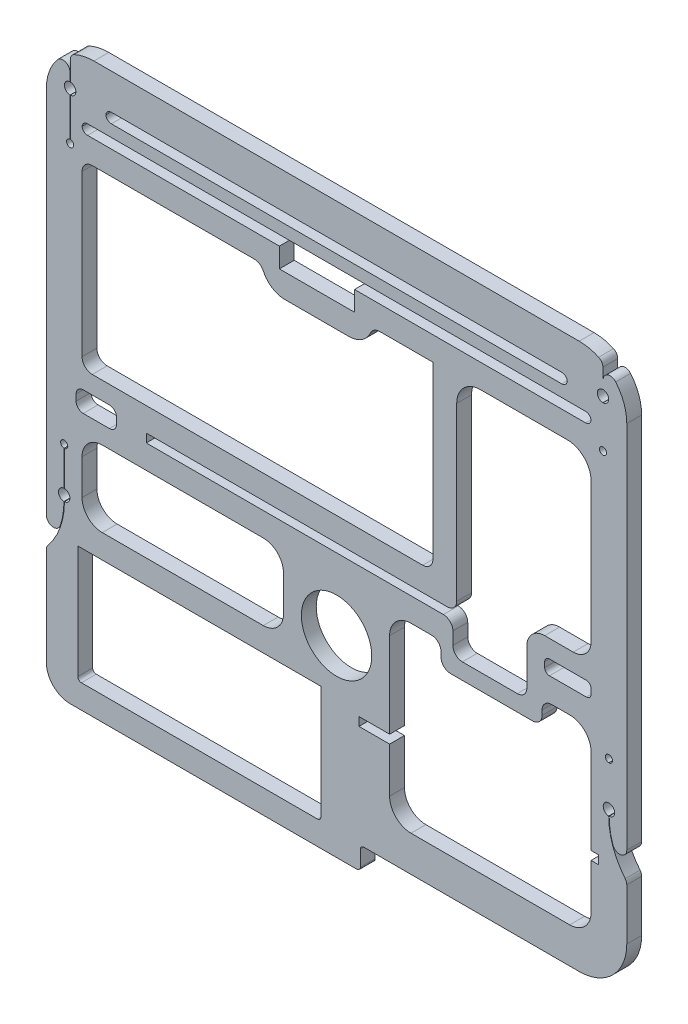
SolidWorks part; units mm, degrees
ref_plane "Front Plane" through (0, 0, 0) normal (0, 0, 1) x (1, 0, 0)
ref_plane "Top Plane" through (0, 0, 0) normal (0, 1, 0) x (1, 0, 0)
ref_plane "Right Plane" through (0, 0, 0) normal (1, 0, 0) x (0, 0, -1)
sketch "Sketch1" plane through (0, 0, 0) normal (0, 0, 1) x (1, 0, 0)
  line L0 (63.9883, 88.3985) -> (63.9883, 84.5885) construction
  line L1 (48.2422, 30.1083) -> (110.2188, 30.1083)
  line L2 (48.2422, 30.1083) -> (48.2422, 88.3985)
  line L3 (48.2422, 88.3985) -> (110.2188, 88.3985)
  line L4 (110.2188, 30.1083) -> (110.2188, 88.3985)
  line L5 (106.4088, 84.5885) -> (52.0522, 84.5885)
  line L6 (106.4088, 84.5885) -> (106.4088, 33.9183)
  line L7 (106.4088, 33.9183) -> (52.0522, 33.9183)
  line L8 (52.0522, 84.5885) -> (52.0522, 33.9183)
  line L9 (63.9883, 86.4935) -> (18.0707, 86.4935) construction
  line L10 (52.0522, 41.2855) -> (48.2422, 41.2855) construction
  line L11 (50.1472, 41.2855) -> (50.1472, 25.8577) construction
  line L12 (13.5248, 33.9183) -> (13.5248, 30.1083) construction
  line L13 (13.5248, 32.0133) -> (21.1598, 32.0133) construction
  line L14 (110.2188, 38.1916) -> (106.4088, 38.1916) construction
  line L15 (108.3138, 38.1916) -> (108.3138, 22.3321) construction
  line L16 (106.4088, 54.6152) -> (106.4088, 79.5085) construction
  line L17 (52.0522, 74.5555) -> (52.0522, 54.6152) construction
  line L22 (79.0876, 86.4935) -> (79.6338, 86.4935) construction
  line L23 (96.5564, 32.0133) -> (96.0102, 32.0133) construction
  dimension "D1" = 3.81
  dimension "D2" = 3.81
extrude "Boss-Extrude1" add sketch "Sketch1" along normal blind 1.5875
sketch "Sketch2" plane through (0, 0, 0) normal (0, 0, -1) x (-1, 0, 0)
  line L0 (-106.4088, 33.9183) -> (-106.4088, 84.5885) construction
  line L1 (-106.4088, 55.8724) -> (-52.0522, 55.8724)
  line L2 (-106.4088, 55.8724) -> (-106.4088, 53.3324)
  line L3 (-106.4088, 53.3324) -> (-52.0522, 53.3324)
  line L4 (-52.0522, 55.8724) -> (-52.0522, 53.3324)
  line L5 (-52.0522, 84.5885) -> (-52.0522, 33.9183) construction
  line L7 (-99.5505, 55.8724) -> (-58.9105, 55.8724) construction
  line L8 (-99.4108, 81.1849) -> (-61.0568, 81.1849) construction
  line L9 (-80.5132, 79.0767) -> (-73.7568, 79.0767) construction
  line L10 (-80.5132, 81.1849) -> (-80.5132, 79.0767) construction
  line L11 (-106.4088, 81.1849) -> (-81.1482, 81.1849)
  line L12 (-106.4088, 81.1849) -> (-106.4088, 78.6449)
  line L13 (-106.4088, 78.6449) -> (-83.0532, 78.6449)
  line L14 (-52.0522, 81.1849) -> (-52.0522, 78.6449)
  line L15 (-106.4088, 83.5217) -> (-52.0522, 83.5217)
  line L16 (-106.4088, 83.5217) -> (-106.4088, 82.2517)
  line L17 (-106.4088, 82.2517) -> (-52.0522, 82.2517)
  line L18 (-52.0522, 83.5217) -> (-52.0522, 82.2517)
  line L19 (-73.7568, 79.0767) -> (-73.7568, 81.1849) construction
  line L20 (-80.5132, 81.1849) -> (-80.5132, 79.0767) construction
  line L21 (-73.7568, 79.0767) -> (-73.7568, 81.1849) construction
  line L22 (-81.1482, 79.0767) -> (-81.1482, 81.1849)
  line L23 (-73.1218, 79.0767) -> (-81.1482, 79.0767)
  line L24 (-73.1218, 79.0767) -> (-73.1218, 81.1849)
  line L25 (-83.0532, 78.6449) -> (-83.0532, 76.5367)
  line L26 (-83.0532, 76.5367) -> (-71.2168, 76.5367)
  line L27 (-71.2168, 76.5367) -> (-71.2168, 78.6449)
  line L28 (-71.2168, 78.6449) -> (-52.0522, 78.6449)
  line L29 (-73.1218, 81.1849) -> (-52.0522, 81.1849)
  line L30 (-81.1482, 71.7401) -> (-80.5132, 71.7401) construction
  line L31 (-57.9086, 84.5885) -> (-57.9086, 83.5217) construction
  line L32 (-73.7568, 71.6584) -> (-73.1218, 71.6584) construction
  line L33 (-106.4088, 84.5885) -> (-52.0522, 84.5885) construction
  line L35 (-57.9086, 82.2517) -> (-57.9086, 81.1849) construction
  dimension "D1" = 2.54
  dimension "D2" = 1.905
  dimension "D3" = 2.54
  dimension "D4" = 1.905
  dimension "D5" = 1.27
  dimension "D6" = 0.635
extrude "Boss-Extrude2" add sketch "Sketch2" against normal up to surface (1.5875 mm away) up to face at (79.2305, 59.2534, 1.5875)
sketch "Sketch3" plane through (0, 0, 0) normal (0, 0, -1) x (-1, 0, 0)
  line L0 (-92.0575, 59.3268) -> (-92.0575, 56.7868) construction
  line L3 (-58.9105, 56.7868) -> (-99.5505, 56.7868) construction
  line L12 (-92.0575, 56.7868) -> (-13.0532, 56.7868)
  line L13 (-13.0532, 56.7868) -> (-52.0522, 56.7868)
  line L14 (-52.0522, 78.6449) -> (-52.0522, 55.8724) construction
  line L15 (-52.0522, 56.7868) -> (-52.0522, 59.3268)
  line L16 (-52.0522, 59.3268) -> (-89.5175, 59.3268)
  line L17 (-89.5175, 59.3268) -> (-89.5175, 78.6449)
  line L18 (-71.2168, 78.6449) -> (-52.0522, 78.6449) construction
  line L19 (-89.5175, 78.6449) -> (-92.0575, 78.6449)
  line L20 (-92.0575, 78.6449) -> (-92.0575, 56.7868)
  line M27 (-71.2168, 78.6449) -> (-52.0522, 78.6449)
  line M28 (-52.0522, 78.6449) -> (-52.0522, 55.8724)
  dimension "D3" = 2.54
  dimension "D4" = 2.54
extrude "Boss-Extrude3" add sketch "Sketch3" against normal up to surface (1.5875 mm away) contours L20 L12 L13 L16 L17 M27 M28 region at (91.6016, 67.7159, 0) up to face at (79.2305, 84.0551, 1.5875)
sketch "Sketch14" plane through (0, 0, 1.5875) normal (0, 0, 1) x (1, 0, 0)
  line L0 (77.0492, 42.694) -> (51.5984, 42.694) construction
  line L1 (84.8947, 41.932) -> (84.8947, 50.7924) construction
  line L2 (84.8947, 33.9183) -> (84.8947, 53.3324)
  line L4 (77.0492, 42.694) -> (52.0522, 42.694)
  line L5 (52.0522, 53.3324) -> (52.0522, 33.9183) construction
  line L6 (52.0522, 53.3324) -> (106.4088, 53.3324) construction
  line L7 (52.0522, 33.9183) -> (106.4088, 33.9183) construction
  line L9 (77.0492, 42.694) -> (77.0492, 33.9183)
  line L10 (77.0492, 33.9183) -> (84.8947, 33.9183)
  line L11 (52.0522, 53.3324) -> (84.8947, 53.3324)
  line L12 (52.0522, 53.3324) -> (52.0522, 42.694)
extrude "Boss-Extrude9" add sketch "Sketch14" against normal up to surface (1.5875 mm away) up to face at (83.5062, 63.768, 0)
sketch "Sketch5" plane through (0, 0, 0) normal (0, 0, -1) x (-1, 0, 0)
  line L1 (-51.5984, 30.2353) -> (-77.5572, 30.2353) construction
  line L2 (-51.5984, 30.2353) -> (-51.5984, 42.694) construction
  line L6 (-51.5984, 42.694) -> (-77.5572, 42.694) construction
  line L7 (-77.5572, 30.2353) -> (-77.5572, 42.694) construction
  line L8 (-51.5984, 30.2353) -> (-77.5572, 30.2353)
  line L9 (-51.5984, 30.2353) -> (-51.5984, 42.694)
  line L10 (-51.5984, 42.694) -> (-77.5572, 42.694)
  line L11 (-77.5572, 30.2353) -> (-77.5572, 42.694)
  circle A1 centre (-79.2305, 48.2171) radius 3.7592 construction
  circle A2 centre (-79.2305, 48.2171) radius 3.7592
extrude "Cut-Extrude1" cut sketch "Sketch5" against normal up to surface (1.5875 mm away) up to face at (64.5507, 38.3062, 1.5875)
fillet "Fillet1" radius 5.08 3 edges at (110.2188, 30.1083, 0.7937) (48.2422, 88.3985, 0.7937) (110.2188, 88.3985, 0.7937)
fillet "Fillet2" radius 2.54 4 edges at (71.2168, 76.5367, 0.7937) (106.4088, 78.6449, 0.7937) (83.0532, 76.5367, 0.7937) (92.0575, 78.6449, 0.7937)
fillet "Fillet3" radius 1.0922 5 edges at (52.0522, 59.3268, 0.7937) (89.5175, 59.3268, 0.7937) (52.0522, 78.6449, 0.7937) (71.2168, 78.6449, 0.7937) (83.0532, 78.6449, 0.7937)
fillet "Fillet4" radius 0.5842 4 edges at (52.0522, 81.1849, 0.7937) (52.0522, 82.2517, 0.7938) (106.4088, 82.2517, 0.7937) (106.4088, 81.1849, 0.7937)
sketch "Sketch6" plane through (0, 0, 0) normal (0, 0, -1) x (-1, 0, 0)
  circle A0 centre (-107.6788, 84.5885) radius 0.6096 construction
  circle A1 centre (-50.7822, 84.5885) radius 0.6096 construction
  circle A2 centre (-108.3138, 46.6777) radius 0.6096 construction
  circle A3 centre (-50.1472, 46.6777) radius 0.6096 construction
  circle A4 centre (-107.6788, 84.5885) radius 0.6096
  circle A5 centre (-50.7822, 84.5885) radius 0.6096
  circle A6 centre (-108.3138, 46.6777) radius 0.6096
  circle A7 centre (-50.1472, 46.6777) radius 0.6096
extrude "Cut-Extrude2" cut sketch "Sketch6" against normal up to surface (1.5875 mm away) up to face at (75.4713, 48.2171, 1.5875)
sketch "Sketch9" plane through (0, 0, 1.5875) normal (0, 0, 1) x (1, 0, 0)
  line L4 (107.199, 41.932) -> (81.6212, 41.932)
  line L5 (81.6212, 41.932) -> (81.6212, 41.0176)
  line L6 (81.6212, 41.0176) -> (107.199, 41.0176)
  line L7 (107.199, 41.0176) -> (107.199, 41.932)
  line L8 (107.199, 41.932) -> (81.6212, 41.932)
  line L9 (81.6212, 41.932) -> (81.6212, 41.0176)
  line L10 (81.6212, 41.0176) -> (107.199, 41.0176)
  line L11 (107.199, 41.0176) -> (107.199, 41.932)
  dimension "D1" = 0
extrude "Cut-Extrude3" cut sketch "Sketch9" against normal up to surface (1.5875 mm away) up to face at (49.5376, 46.6777, 0)
sketch "Sketch11" plane through (0, 0, 1.5875) normal (0, 0, 1) x (1, 0, 0)
  line L0 (51.5984, 30.2353) -> (77.5572, 30.2353) construction
  line L1 (48.2422, 30.1083) -> (81.7705, 30.1083)
  line L2 (48.2422, 30.1083) -> (48.2422, 27.6953)
  line L3 (48.2422, 27.6953) -> (81.7705, 27.6953)
  line L4 (81.7705, 30.1083) -> (81.7705, 27.6953)
  line L5 (79.2305, 51.9763) -> (79.2305, -22.2214) construction
  circle A0 centre (79.2305, 48.2171) radius 3.7592 construction
  dimension "D1" = 2.54
  dimension "D2" = 2.54
extrude "Boss-Extrude6" add sketch "Sketch11" against normal up to surface (1.5875 mm away) up to face at (95.2379, 42.1917, 0)
fillet "Fillet7" radius 2.54 1 edges at (48.2422, 27.6953, 0.7937)
fillet "Fillet8" radius 0.381 2 edges at (81.7705, 27.6953, 0.7937) (81.7705, 30.1083, 0.7937)
sketch "Sketch12" plane through (0, 0, 1.5875) normal (0, 0, 1) x (1, 0, 0)
  line L0 (52.0522, 84.5885) -> (52.0522, 83.5217) construction
  line L1 (52.0522, 84.5885) -> (54.5922, 84.5885)
  line L2 (52.0522, 84.5885) -> (52.0522, 83.5217)
  line L3 (52.0522, 83.5217) -> (54.5922, 83.5217)
  line L4 (54.5922, 84.5885) -> (54.5922, 83.5217)
  line L5 (106.4088, 84.5885) -> (52.0522, 84.5885) construction
  line L6 (106.4088, 83.5217) -> (52.0522, 83.5217) construction
  line L8 (106.4088, 84.5885) -> (103.8688, 84.5885)
  line L9 (106.4088, 84.5885) -> (106.4088, 83.5217)
  line L10 (106.4088, 83.5217) -> (103.8688, 83.5217)
  line L11 (103.8688, 84.5885) -> (103.8688, 83.5217)
  dimension "D1" = 2.54
extrude "Boss-Extrude7" add sketch "Sketch12" against normal up to surface (1.5875 mm away) up to face at (95.2379, 42.1917, 0)
fillet "Fillet11" radius 0.5842 4 edges at (103.8688, 83.5217, 0.7937) (103.8688, 84.5885, 0.7937) (54.5922, 83.5217, 0.7937) (54.5922, 84.5885, 0.7937)
sketch "Sketch13" plane through (0, 0, 1.5875) normal (0, 0, 1) x (1, 0, 0)
  line L0 (50.7695, 86.0858) -> (50.7695, 85.198) construction
  line L1 (50.7949, 85.198) -> (50.7949, 87.2592) construction
  line L2 (50.7695, 83.9791) -> (50.7695, 79.8893) construction
  line L3 (50.7949, 79.8893) -> (50.7949, 83.9791) construction
  line L4 (107.6661, 85.198) -> (107.6661, 87.2592) construction
  line L5 (107.6915, 83.9791) -> (107.6915, 79.8893) construction
  line L6 (107.6661, 79.8893) -> (107.6661, 83.9791) construction
  line L7 (108.3265, 50.9963) -> (108.3265, 47.2872) construction
  line L8 (108.3011, 50.9963) -> (108.3011, 47.2872) construction
  line L9 (50.1345, 50.9963) -> (50.1345, 47.2872) construction
  line L10 (50.1599, 50.9963) -> (50.1599, 47.2872) construction
  line L11 (50.7695, 86.0858) -> (50.7695, 85.198)
  line L12 (50.7949, 85.198) -> (50.7949, 87.2592)
  line L13 (50.7695, 83.9791) -> (50.7695, 79.8893)
  line L14 (50.7949, 79.8893) -> (50.7949, 83.9791)
  line L15 (107.6661, 85.198) -> (107.6661, 87.2592)
  line L16 (107.6915, 83.9791) -> (107.6915, 79.8893)
  line L17 (107.6661, 79.8893) -> (107.6661, 83.9791)
  line L18 (108.3265, 50.9963) -> (108.3265, 47.2872)
  line L19 (108.3011, 50.9963) -> (108.3011, 47.2872)
  line L20 (50.1345, 50.9963) -> (50.1345, 47.2872)
  line L21 (50.1599, 50.9963) -> (50.1599, 47.2872)
  line L22 (48.2422, 83.3185) -> (48.2422, 30.2353) construction
  line L23 (110.2188, 35.1883) -> (110.2188, 83.3185) construction
  line L24 (48.2422, 43.8754) -> (48.2422, 40.6699)
  line L25 (110.2188, 40.6699) -> (110.2188, 43.8754)
  line L26 (107.6915, 83.9791) -> (107.6915, 79.8893)
  line L27 (107.6915, 86.0858) -> (107.6915, 85.198) construction
  line L28 (107.6915, 86.0858) -> (107.6915, 85.198)
  arc A0 (107.6661, 83.9791) -> (107.6915, 83.9791) centre (107.6788, 84.5885) ccw
  arc A1 (50.7695, 86.0858) -> (49.4225, 86.5742) centre (50.0075, 86.0858) ccw construction
  arc A2 (51.2454, 87.9546) -> (50.7949, 87.2592) centre (51.5569, 87.2592) ccw construction
  arc A3 (50.7695, 79.8893) -> (50.7949, 79.8893) centre (50.7822, 79.5085) ccw construction
  arc A4 (107.6661, 87.2592) -> (107.2156, 87.9546) centre (106.9041, 87.2592) ccw construction
  arc A5 (109.0384, 86.5742) -> (107.6915, 86.0858) centre (108.4535, 86.0858) ccw construction
  arc A6 (107.6661, 79.8893) -> (107.6915, 79.8893) centre (107.6788, 79.5085) ccw construction
  arc A7 (108.3265, 50.9963) -> (108.3011, 50.9963) centre (108.3138, 51.3771) ccw construction
  arc A8 (108.3392, 46.0687) -> (108.7338, 43.6346) centre (116.0396, 46.0681) ccw construction
  arc A9 (108.7338, 43.6346) -> (110.2188, 43.8754) centre (109.4568, 43.8754) ccw construction
  arc A10 (108.2884, 46.0687) -> (110.046, 41.153) centre (116.0396, 46.0681) ccw construction
  arc A11 (110.2188, 40.6699) -> (110.046, 41.153) centre (109.4568, 40.6699) ccw construction
  arc A12 (48.2422, 43.8754) -> (49.7271, 43.6346) centre (49.0042, 43.8754) ccw construction
  arc A13 (50.1599, 50.9963) -> (50.1345, 50.9963) centre (50.1472, 51.3771) ccw construction
  arc A14 (48.415, 41.153) -> (50.1726, 46.0687) centre (42.4214, 46.0681) ccw construction
  arc A15 (49.7271, 43.6346) -> (50.1218, 46.0687) centre (42.4214, 46.0681) ccw construction
  arc A16 (48.415, 41.153) -> (48.2422, 40.6699) centre (49.0042, 40.6699) ccw construction
  arc A17 (50.7695, 83.9791) -> (50.7949, 83.9791) centre (50.7822, 84.5885) ccw
  arc A18 (50.7695, 86.0858) -> (49.4225, 86.5742) centre (50.0075, 86.0858) ccw
  arc A19 (51.2454, 87.9546) -> (50.7949, 87.2592) centre (51.5569, 87.2592) ccw
  arc A20 (50.7695, 79.8893) -> (50.7949, 79.8893) centre (50.7822, 79.5085) ccw
  arc A21 (107.6661, 87.2592) -> (107.2156, 87.9546) centre (106.9041, 87.2592) ccw
  arc A22 (109.0384, 86.5742) -> (107.6915, 86.0858) centre (108.4535, 86.0858) ccw
  arc A23 (107.6661, 79.8893) -> (107.6915, 79.8893) centre (107.6788, 79.5085) ccw
  arc A24 (108.3265, 50.9963) -> (108.3011, 50.9963) centre (108.3138, 51.3771) ccw
  arc A25 (108.3392, 46.0687) -> (108.7338, 43.6346) centre (116.0396, 46.0681) ccw
  arc A26 (108.7338, 43.6346) -> (110.2188, 43.8754) centre (109.4568, 43.8754) ccw
  arc A27 (108.2884, 46.0687) -> (110.046, 41.153) centre (116.0396, 46.0681) ccw
  arc A28 (110.2188, 40.6699) -> (110.046, 41.153) centre (109.4568, 40.6699) ccw
  arc A29 (48.2422, 43.8754) -> (49.7271, 43.6346) centre (49.0042, 43.8754) ccw
  arc A30 (50.1599, 50.9963) -> (50.1345, 50.9963) centre (50.1472, 51.3771) ccw
  arc A31 (48.415, 41.153) -> (50.1726, 46.0687) centre (42.4214, 46.0681) ccw
  arc A32 (49.7271, 43.6346) -> (50.1218, 46.0687) centre (42.4214, 46.0681) ccw
  arc A33 (48.415, 41.153) -> (48.2422, 40.6699) centre (49.0042, 40.6699) ccw
  circle A34 centre (50.7822, 84.5885) radius 0.6096 construction
  circle A35 centre (107.6788, 84.5885) radius 0.6096 construction
  circle A36 centre (108.3138, 46.6777) radius 0.6096 construction
  circle A37 centre (50.1472, 46.6777) radius 0.6096 construction
  arc A38 (53.3222, 88.3985) -> (48.2422, 83.3185) centre (53.3222, 83.3185) ccw construction
  arc A39 (110.2188, 83.3185) -> (105.1388, 88.3985) centre (105.1388, 83.3185) ccw construction
  arc A40 (50.7949, 85.198) -> (50.7695, 85.198) centre (50.7822, 84.5885) ccw
  arc A41 (107.6661, 83.9791) -> (107.6915, 83.9791) centre (107.6788, 84.5885) ccw
  arc A42 (108.3265, 47.2872) -> (108.3011, 47.2872) centre (108.3138, 46.6777) ccw
  arc A43 (50.1218, 46.0687) -> (50.1726, 46.0687) centre (50.1472, 46.6777) ccw
  arc A44 (51.2454, 87.9546) -> (49.4225, 86.5742) centre (53.3222, 83.3185) ccw
  arc A45 (109.0384, 86.5742) -> (107.2156, 87.9546) centre (105.1388, 83.3185) ccw
  arc A46 (50.1599, 47.2872) -> (50.1345, 47.2872) centre (50.1472, 46.6777) ccw
  arc A47 (108.2884, 46.0687) -> (108.3392, 46.0687) centre (108.3138, 46.6777) ccw
  arc A48 (107.6915, 85.198) -> (107.6661, 85.198) centre (107.6788, 84.5885) ccw
extrude "Cut-Extrude4" cut sketch "Sketch13" against normal through all contours A48 L28 A22 A45 A21 L15 | L17 A23 L16 A0 | A47 A27 A28 L25 A26 A25 | A42 L18 A24 L19 | A43 A32 A29 L24 A33 A31 | A46 L21 A30 L20 | A19 A44 A18 L11 A40 L12 | L13 A20 L14 A17 region at (50.4642, 87.0334, 1.5875) region at (50.7822, 79.9586, 1.5875) region at (107.9968, 87.0334, 1.5875) region at (107.6788, 79.9586, 1.5875) region at (108.3138, 50.9944, 1.5875) region at (50.1472, 50.9944, 1.5875) region at (48.8136, 42.5993, 1.5875) region at (109.6474, 42.5993, 1.5875)
fillet "Fillet12" radius 2.286 4 edges at (106.4088, 33.9183, 0.7937) (106.4088, 53.3324, 0.7937) (84.8947, 33.9183, 0.7937) (84.8947, 53.3324, 0.7937)
fillet "Fillet13" radius 0.381 2 edges at (51.5984, 30.2353, 0.7937) (77.5572, 30.2353, 0.7937)
sketch "Sketch15" plane through (0, 0, 1.5875) normal (0, 0, 1) x (1, 0, 0)
  line L0 (73.5663, 51.1734) -> (73.5663, 47.393) construction
  line L1 (71.4073, 45.234) -> (54.2112, 45.234) construction
  line L2 (52.0522, 51.1734) -> (52.0522, 47.393) construction
  line L3 (54.2112, 53.3324) -> (71.4073, 53.3324) construction
  line L4 (73.5663, 51.1734) -> (73.5663, 47.393)
  line L5 (71.4073, 45.234) -> (54.2112, 45.234)
  line L6 (52.0522, 51.1734) -> (52.0522, 47.393)
  line L7 (54.2112, 53.3324) -> (71.4073, 53.3324)
  arc A0 (73.5663, 51.1734) -> (71.4073, 53.3324) centre (71.4073, 51.1734) ccw construction
  arc A1 (71.4073, 45.234) -> (73.5663, 47.393) centre (71.4073, 47.393) ccw construction
  arc A2 (52.0522, 47.393) -> (54.2112, 45.234) centre (54.2112, 47.393) ccw construction
  arc A3 (54.2112, 53.3324) -> (52.0522, 51.1734) centre (54.2112, 51.1734) ccw construction
  arc A4 (73.5663, 51.1734) -> (71.4073, 53.3324) centre (71.4073, 51.1734) ccw
  arc A5 (71.4073, 45.234) -> (73.5663, 47.393) centre (71.4073, 47.393) ccw
  arc A6 (52.0522, 47.393) -> (54.2112, 45.234) centre (54.2112, 47.393) ccw
  arc A7 (54.2112, 53.3324) -> (52.0522, 51.1734) centre (54.2112, 51.1734) ccw
extrude "Cut-Extrude5" cut sketch "Sketch15" against normal through all
sketch "Sketch16" plane through (0, 0, 0) normal (0, 0, -1) x (-1, 0, 0)
  line L1 (-104.1228, 53.3324) -> (-87.1807, 53.3324) construction
  line L2 (-98.6361, 53.7769) -> (-98.6361, 55.8724) construction
  line L3 (-101.1761, 53.3324) -> (-90.3811, 53.3324)
  line L4 (-101.1761, 53.3324) -> (-101.1761, 50.7924)
  line L5 (-101.1761, 50.7924) -> (-90.3811, 50.7924)
  line L6 (-90.3811, 53.3324) -> (-90.3811, 50.7924)
  line L7 (-92.9211, 53.7769) -> (-92.9211, 55.8724) construction
  dimension "D1" = 2.54
  dimension "D2" = 2.54
  dimension "D3" = 2.54
extrude "Boss-Extrude10" add sketch "Sketch16" against normal up to surface (1.5875 mm away) up to face at (62.8092, 49.2832, 1.5875)
sketch "Sketch17" plane through (0, 0, 0) normal (0, 0, -1) x (-1, 0, 0)
  line L0 (-52.0522, 55.8724) -> (-106.4088, 55.8724) construction
  line L1 (-99.5505, 55.8724) -> (-91.6511, 55.8724)
  line L2 (-99.5505, 55.8724) -> (-99.5505, 52.5069)
  line L3 (-99.5505, 52.5069) -> (-91.6511, 52.5069)
  line L4 (-91.6511, 55.8724) -> (-91.6511, 52.5069)
  line L5 (-93.5561, 53.7769) -> (-92.9211, 53.7769) construction
  line L6 (-92.9211, 53.7769) -> (-92.9211, 55.8724) construction
  line L8 (-99.5505, 56.7868) -> (-99.5505, 55.8724) construction
  dimension "D1" = 1.27
  dimension "D2" = 1.27
extrude "Cut-Extrude6" cut sketch "Sketch17" against normal up to next
fillet "Fillet14" radius 1.016 8 edges at (91.6511, 55.8724, 0.7937) (99.5505, 52.5069, 0.7937) (91.6511, 52.5069, 0.7937) (90.3811, 53.3324, 0.7938) (90.3811, 50.7924, 0.7938) (101.1761, 50.7924, 0.7938) (101.1761, 53.3324, 0.7937) (92.0575, 56.7868, 0.7937)
sketch "Sketch18" plane through (0, 0, 0) normal (0, 0, -1) x (-1, 0, 0)
  line L0 (-99.5505, 55.8724) -> (-99.5505, 59.3268)
  line L1 (-99.5505, 59.3268) -> (-106.4088, 59.3268)
  line L2 (-106.4088, 55.8724) -> (-106.4088, 76.1049) construction
  line L3 (-101.4555, 55.8724) -> (-101.4555, 57.4218)
  line L4 (-99.5505, 55.8724) -> (-106.4088, 55.8724) construction
  line L5 (-101.4555, 57.4218) -> (-106.4088, 57.4218)
  line L6 (-106.4088, 57.4218) -> (-106.4088, 59.3268)
  line L7 (-99.5505, 56.7868) -> (-58.9105, 56.7868) construction
  line L18 (-92.0575, 57.8028) -> (-92.0575, 76.1049)
  line L19 (-52.0522, 56.7868) -> (-91.0415, 56.7868)
  line L20 (-52.0522, 55.8724) -> (-52.0522, 56.7868)
  line L21 (-90.6351, 55.8724) -> (-52.0522, 55.8724)
  line L22 (-91.6511, 53.5229) -> (-91.6511, 54.8564)
  line L23 (-98.5345, 52.5069) -> (-92.6671, 52.5069)
  line L24 (-99.5505, 55.8724) -> (-99.5505, 53.5229)
  line L25 (-106.4088, 55.8724) -> (-99.5505, 55.8724)
  line L26 (-106.4088, 76.1049) -> (-106.4088, 55.8724)
  line L27 (-94.5975, 78.6449) -> (-103.8688, 78.6449)
  line L35 (-101.4555, 55.8724) -> (-99.5505, 55.8724)
  arc A6 (-92.0575, 76.1049) -> (-94.5975, 78.6449) centre (-94.5975, 76.1049) ccw
  arc A7 (-92.0575, 57.8028) -> (-91.0415, 56.7868) centre (-91.0415, 57.8028) ccw
  arc A8 (-90.6351, 55.8724) -> (-91.6511, 54.8564) centre (-90.6351, 54.8564) ccw
  arc A9 (-92.6671, 52.5069) -> (-91.6511, 53.5229) centre (-92.6671, 53.5229) ccw
  arc A10 (-99.5505, 53.5229) -> (-98.5345, 52.5069) centre (-98.5345, 53.5229) ccw
  arc A11 (-92.0575, 76.1049) -> (-94.5975, 78.6449) centre (-94.5975, 76.1049) ccw
  arc A12 (-103.8688, 78.6449) -> (-106.4088, 76.1049) centre (-103.8688, 76.1049) ccw
  dimension "D1" = 1.905
  dimension "D2" = 1.905
  dimension "D3" = 2.54
  dimension "D4" = 0
extrude "Boss-Extrude11" add sketch "Sketch18" against normal up to surface (1.5875 mm away) contours L3 L35 L0 L1 L6 L5 region at (102.5232, 58.056, 0) up to face at (90.9503, 60.7445, 1.5875)
fillet "Fillet15" radius 0.508 4 edges at (106.4088, 55.8724, 0.7937) (106.4088, 57.4218, 0.7937) (101.4555, 57.4218, 0.7938) (101.4555, 55.8724, 0.7938)
sketch "Sketch19" plane through (0, 0, 0) normal (0, 0, -1) x (-1, 0, 0)
  line L0 (-58.9105, 56.7868) -> (-58.9105, 55.8724) construction
  line L1 (-58.9105, 56.7868) -> (-58.9105, 55.8724)
  line L2 (-52.0522, 55.8724) -> (-90.6351, 55.8724) construction
  line L3 (-52.0522, 56.7868) -> (-52.0522, 55.8724) construction
  line L4 (-91.0415, 56.7868) -> (-52.0522, 56.7868) construction
  line L5 (-52.0522, 55.8724) -> (-58.9105, 55.8724)
  line L6 (-52.0522, 56.7868) -> (-52.0522, 55.8724)
  line L7 (-58.9105, 56.7868) -> (-52.0522, 56.7868)
extrude "Boss-Extrude12" add sketch "Sketch19" against normal up to surface (1.5875 mm away) up to face at (103.9321, 56.6471, 1.5875)
sketch "Sketch20" plane through (0, 0, 0) normal (0, 0, -1) x (-1, 0, 0)
  line L0 (-58.9105, 56.3296) -> (-55.7355, 56.3296) construction
  line L1 (-55.7355, 57.4218) -> (-51.4172, 57.4218)
  line L2 (-55.7355, 57.4218) -> (-55.7355, 55.2374)
  line L3 (-55.7355, 55.2374) -> (-51.4172, 55.2374)
  line L4 (-51.4172, 57.4218) -> (-51.4172, 55.2374)
  line L5 (-58.9105, 56.7868) -> (-58.9105, 55.8724) construction
  line L6 (-48.2422, 83.3185) -> (-48.2422, 43.8754) construction
  line L7 (-51.4172, 56.3296) -> (-48.2422, 56.3296) construction
  line L8 (-54.6015, 59.3268) -> (-54.6015, 57.4218) construction
  line L9 (-53.1444, 59.3268) -> (-88.4253, 59.3268) construction
  line L11 (-54.6015, 55.2374) -> (-54.6015, 53.3324) construction
  line L12 (-71.4073, 53.3324) -> (-54.2112, 53.3324) construction
  point P8 (-55.7355, 56.3296)
  dimension "D1" = 3.175
  dimension "D2" = 1.905
extrude "Cut-Extrude7" cut sketch "Sketch20" against normal through all
fillet "Fillet16" radius 0.762 4 edges at (55.7355, 55.2374, 0.7938) (51.4172, 57.4218, 0.7938) (51.4172, 55.2374, 0.7937) (55.7355, 57.4218, 0.7938)
fillet "Fillet17" radius 1.905 2 edges at (99.5505, 59.3268, 0.7938) (106.4088, 59.3268, 0.7938)
